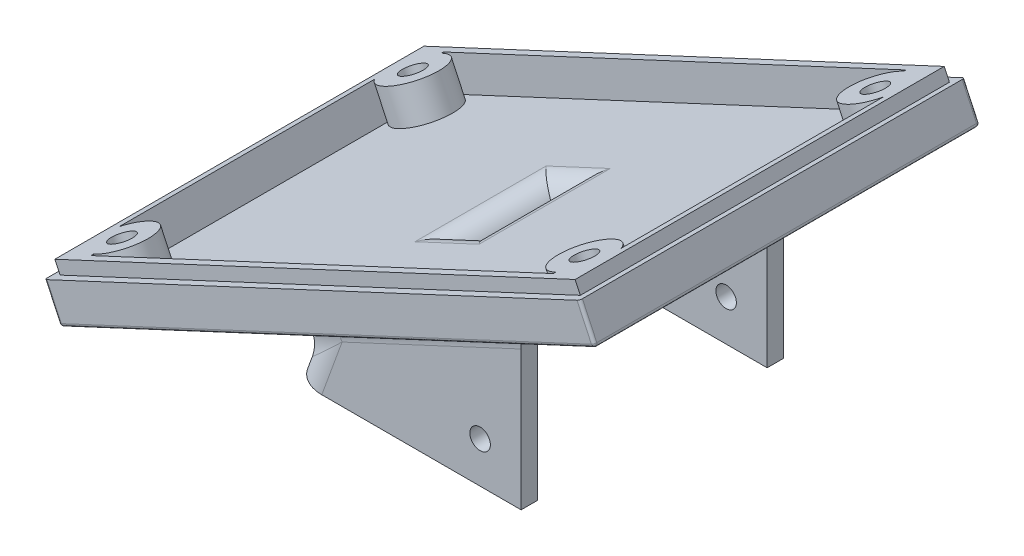
SolidWorks part; units mm, degrees
material "ABS"
ref_plane "Front Plane" through (0, 0, 0) normal (0, 0, 1) x (1, 0, 0)
ref_plane "Top Plane" through (0, 0, 0) normal (0, 1, 0) x (1, 0, 0)
ref_plane "Right Plane" through (0, 0, 0) normal (1, 0, 0) x (0, 0, -1)
sketch "Sketch1" plane through (0, 0, 0) normal (0, 0, 1) x (1, 0, 0)
  line L1 (14.28, 10) -> (-14.28, 10)
  line L2 (14.28, 10) -> (14.28, -10)
  line L3 (14.28, -10) -> (-14.28, -10)
  line L4 (-14.28, 10) -> (-14.28, -10)
  line L5 (14.28, 10) -> (-14.28, -10) construction
  line L6 (14.28, -10) -> (-14.28, 10) construction
  point P0 (0, 0)
  dimension "D1" = 28.56
  dimension "D2" = 20
extrude "Boss-Extrude1" add sketch "Sketch1" along normal blind 2
sketch "Sketch2" plane through (0, 0, 2) normal (0, 0, 1) x (1, 0, 0)
  line L0 (-14.28, -9.9979) -> (14.28, 10)
  line L1 (14.28, 10) -> (-14.28, 10)
  line L2 (-14.28, 10) -> (-14.28, -9.9979)
  line L3 (-14.28, -10) -> (14.28, -10) construction
  line L4 (14.28, -10) -> (14.28, 10) construction
  dimension "D1" = 35
  dimension "D2" = 0
extrude "Boss-Extrude2" add sketch "Sketch2" along normal blind 28
sketch "Sketch3" plane through (0, 0, 30) normal (0, 0, 1) x (1, 0, 0)
  line L1 (-14.28, 10) -> (14.28, 10)
  line L2 (-14.28, 10) -> (-14.28, -10)
  line L3 (-14.28, -10) -> (14.28, -10)
  line L4 (14.28, 10) -> (14.28, -10)
  dimension "D1" = 20
  dimension "D2" = 28.56
extrude "Boss-Extrude3" add sketch "Sketch3" along normal blind 2
sketch "Sketch4" plane through (0, 0, 32) normal (0, 0, 1) x (1, 0, 0)
  line L0 (14.28, -10) -> (14.28, 10) construction
  line L1 (-14.28, -10) -> (14.28, -10) construction
  circle A0 centre (9.28, -5) radius 1.25
  dimension "D3" = 2.5
  dimension "D1" = 5
  dimension "D2" = 5
extrude "Cut-Extrude1" cut sketch "Sketch4" against normal through all
sketch "Sketch5" plane through (0, 0, 32) normal (0, 0, 1) x (1, 0, 0)
  line L0 (-14.28, 10) -> (-14.28, -1.9188)
  line L1 (-14.28, 10) -> (-14.28, -10) construction
  line L2 (-14.28, -1.9188) -> (11.28, 10)
  line L3 (14.28, 10) -> (-14.28, 10) construction
  line L4 (11.28, 10) -> (-14.28, 10)
  line L5 (14.28, 10) -> (-14.28, 10) construction
  dimension "D1" = 3
  dimension "D2" = 25
extrude "Cut-Extrude2" cut sketch "Sketch5" against normal through all
sketch "Sketch9" plane through (0, 0, 32) normal (0, 0, 1) x (1, 0, 0)
  line L0 (-14.28, -10) -> (-10.7374, -0.2669)
  line L1 (-14.28, -1.9188) -> (11.28, 10) construction
  line L2 (-10.7374, -0.2669) -> (-14.28, -1.9188)
  line L3 (-14.28, -1.9188) -> (-14.28, -10)
  dimension "D1" = 20
extrude "Cut-Extrude5" cut sketch "Sketch9" against normal through all
sketch "Sketch10" plane through (-1.8155, 3.8934, 0) normal (-0.4226, 0.9063, 0) x (0.9063, 0.4226, 0)
  line L0 (-9.8442, 0) -> (14.4493, 0) construction
  line L1 (36, -39.5) -> (-36, -39.5)
  line L2 (36, -39.5) -> (36, 7.5)
  line L3 (36, 7.5) -> (-36, 7.5)
  line L4 (-36, -39.5) -> (-36, 7.5)
  line L5 (36, -39.5) -> (-36, 7.5) construction
  line L6 (36, 7.5) -> (-36, -39.5) construction
  point P0 (0, -16)
  dimension "D1" = 16
  dimension "D2" = 72
  dimension "47mm" = 47
extrude "Boss-Extrude4" add sketch "Sketch10" along normal blind 6
sketch "Sketch11" plane through (-4.3513, 9.3313, 0) normal (-0.4226, 0.9063, 0) x (0.9063, 0.4226, 0)
  line L0 (-36, -39.5) -> (36, -39.5) construction
  line L1 (34, 5.5) -> (-34, 5.5)
  line L2 (34, 5.5) -> (34, -37.5)
  line L3 (34, -37.5) -> (-34, -37.5)
  line L4 (-34, 5.5) -> (-34, -37.5)
  line L5 (36, 7.5) -> (-36, 7.5) construction
  line L6 (36, -39.5) -> (36, 7.5) construction
  line L7 (-36, 7.5) -> (-36, -39.5) construction
  dimension "D1" = 2
  dimension "D2" = 2
  dimension "D3" = 2
  dimension "D4" = 2
extrude "Cut-Extrude6" cut sketch "Sketch11" against normal blind 4
sketch "Sketch14" plane through (-4.3513, 9.3313, 0) normal (-0.4226, 0.9063, 0) x (0.9063, 0.4226, 0)
  line L1 (35, 6.5) -> (-35, 6.5)
  line L2 (35, 6.5) -> (35, -38.5)
  line L3 (35, -38.5) -> (-35, -38.5)
  line L4 (-35, 6.5) -> (-35, -38.5)
  line L5 (-36, -39.5) -> (36, -39.5) construction
  line L6 (34, 5.5) -> (-34, 5.5) construction
  line L7 (-36, 7.5) -> (-36, -39.5) construction
  line L8 (36, -39.5) -> (36, 7.5) construction
  dimension "D1" = 1
  dimension "D2" = 1
  dimension "D3" = 1
  dimension "D4" = 1
extrude "Cut-Extrude7" cut sketch "Sketch14" against normal blind 1.5 flip side to cut
sketch "Sketch15" plane through (-2.6608, 5.7061, 0) normal (-0.4226, 0.9063, 0) x (0.9063, 0.4226, 0)
  line L0 (36, 7.5) -> (-36, 7.5) construction
  line L1 (-36, 7.5) -> (-36, -39.5) construction
  circle A0 centre (-31.25, 1.75) radius 3.5
  circle A1 centre (30.96, 1.75) radius 3.5
  circle A2 centre (-31.25, -33.71) radius 3.5
  circle A3 centre (30.96, -33.71) radius 3.5
  dimension "D1" = 7
  dimension "3,75mm" = 5.75
  dimension "D2" = 4.75
  dimension "D3" = 2
  dimension "D4" = 2
extrude "Boss-Extrude5" add sketch "Sketch15" along normal blind 4
sketch "Sketch16" plane through (-2.6608, 5.7061, 0) normal (-0.4226, 0.9063, 0) x (0.9063, 0.4226, 0)
  line L1 (-34, 5.5) -> (-31.25, 5.5)
  line L2 (-34, 5.5) -> (-34, 1.75)
  line L3 (-34, 1.75) -> (-31.25, 1.75)
  line L4 (-31.25, 5.5) -> (-31.25, 1.75)
  line L5 (34, 5.5) -> (30.96, 5.5)
  line L6 (34, 5.5) -> (34, 1.75)
  line L7 (34, 1.75) -> (30.96, 1.75)
  line L8 (30.96, 5.5) -> (30.96, 1.75)
  line L9 (34, -37.5) -> (30.96, -37.5)
  line L10 (34, -37.5) -> (34, -33.71)
  line L11 (34, -33.71) -> (30.96, -33.71)
  line L12 (30.96, -37.5) -> (30.96, -33.71)
  line L13 (-34, -37.5) -> (-31.25, -37.5)
  line L14 (-34, -37.5) -> (-34, -33.71)
  line L15 (-34, -33.71) -> (-31.25, -33.71)
  line L16 (-31.25, -37.5) -> (-31.25, -33.71)
  arc A0 (34, -31.9755) -> (34, -35.4445) centre (30.96, -33.71) ccw construction
  dimension "D1" = 0
extrude "Boss-Extrude6" add sketch "Sketch16" along normal blind 4
sketch "Sketch17" plane through (-4.3513, 9.3313, 0) normal (-0.4226, 0.9063, 0) x (0.9063, 0.4226, 0)
  circle A0 centre (-31.25, 1.75) radius 1.4
  arc A1 (-34, -0.4151) -> (-31.25, 5.25) centre (-31.25, 1.75) ccw construction
  circle A2 centre (30.96, 1.75) radius 1.4
  circle A3 centre (-31.25, -33.71) radius 1.4
  circle A4 centre (30.96, -33.71) radius 1.4
  dimension "D1" = 0
  dimension "D2" = 0
  dimension "D3" = 2.8
  dimension "D4" = 2
  dimension "D5" = 2
extrude "Cut-Extrude8" cut sketch "Sketch17" against normal through all
sketch "Sketch19" plane through (-1.8155, 3.8934, 0) normal (0.4226, -0.9063, 0) x (0.9063, 0.4226, 0)
  circle A0 centre (-31.25, -1.75) radius 2.75
  circle A1 centre (-31.25, -1.75) radius 1.4 construction
  circle A2 centre (30.96, -1.75) radius 2.75
  circle A3 centre (-31.25, 33.71) radius 2.75
  circle A4 centre (30.96, 33.71) radius 2.75
  dimension "D1" = 0
  dimension "D2" = 5.5
  dimension "D3" = 2
  dimension "D4" = 2
extrude "Cut-Extrude9" cut sketch "Sketch19" against normal blind 2.5
fillet "Fillet1" radius 0.35 8 edges at (29.8606, 21.1469, -7.5) (30.8115, 19.1077, 16) (29.8606, 21.1469, 39.5) (-1.8155, 3.8934, 39.5) (-35.3935, -9.2816, 39.5) (-35.3935, -9.2816, -7.5) (-34.4426, -11.3208, 16) (-1.8155, 3.8934, -7.5)
fillet "Fillet2" radius 4 2 edges at (-12.5087, -5.1335, 0) (-12.5087, -5.1335, 32)
fillet "Fillet5" radius 4 5 edges at (2.8347, 6.0619, 0) (-9.2358, 0.4333, 1.1716) (-10.7374, -0.2669, 16) (-9.2358, 0.4333, 30.8284) (2.8347, 6.0619, 32)
sketch "Sketch20" plane through (-0.0005, 0.0007, 0) normal (0.5736, -0.8192, 0) x (0.8192, 0.5736, 0)
  line L0 (-16.4965, 2) -> (17.4333, 2) construction
  line L1 (1.7184, 21) -> (-0.7816, 21)
  line L2 (1.7184, 21) -> (1.7184, 11)
  line L3 (1.7184, 11) -> (-0.7816, 11)
  line L4 (-0.7816, 21) -> (-0.7816, 11)
  line L5 (1.7184, 21) -> (-0.7816, 11) construction
  line L6 (1.7184, 11) -> (-0.7816, 21) construction
  line L7 (17.4333, 30) -> (17.4333, 2) construction
  point P0 (0.4684, 16)
  point P5 (0.4684, 2)
  point P8 (17.4333, 16)
  dimension "D1" = 10
  dimension "D2" = 0
  dimension "2.5mm" = 2.5
  dimension "D3" = 0
extrude "Cut-Extrude10" cut sketch "Sketch20" against normal through all
fillet "Fillet6" radius 3 4 edges at (-3.2359, 5.4379, 21) (-2.0855, 5.9743, 16) (-3.2359, 5.4379, 11) (-4.3862, 4.9015, 16)
